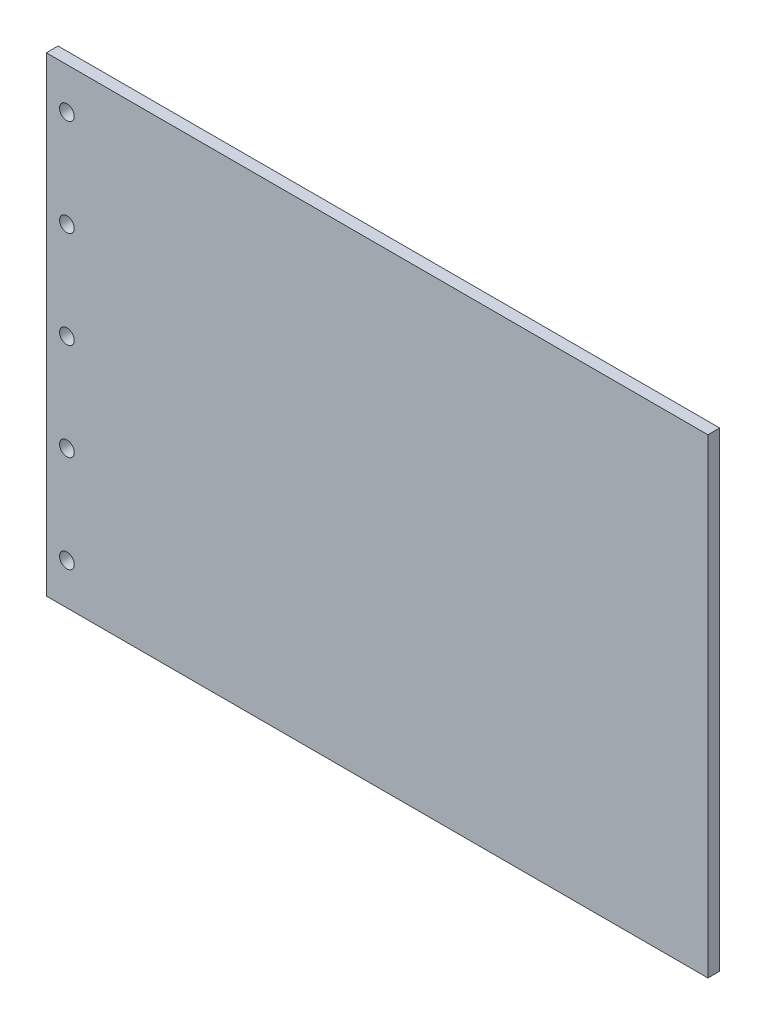
SolidWorks part; units mm, degrees
material "Сталь 3 ГОСТ 535-88"
ref_plane "Спереди" through (0, 0, 0) normal (0, 0, 1) x (1, 0, 0)
ref_plane "Сверху" through (0, 0, 0) normal (0, 1, 0) x (1, 0, 0)
ref_plane "Справа" through (0, 0, 0) normal (1, 0, 0) x (0, 0, -1)
sketch "Эскиз1" plane through (0, 0, 0) normal (0, 0, 1) x (1, 0, 0)
  line L0 (7, 80) -> (0, 80) construction
  line L1 (0, 0) -> (225, 0)
  line L2 (0, 0) -> (0, 160)
  line L3 (0, 160) -> (225, 160)
  line L4 (225, 0) -> (225, 160)
  line L5 (7, 80) -> (7, 0) construction
  line L6 (7, 80) -> (7, 160) construction
  circle A0 centre (7, 80) radius 2.5
  circle A1 centre (7, 47) radius 2.5
  circle A2 centre (7, 14) radius 2.5
  circle A3 centre (7, 113) radius 2.5
  circle A4 centre (7, 146) radius 2.5
  dimension "D3" = 5
  dimension "D4" = 7
  dimension "D5" = 33
  dimension "D6" = 33
  dimension "D7" = 33
  dimension "D8" = 33
  dimension "D1" = 225
  dimension "D2" = 160
extrude "Бобышка-Вытянуть1" add sketch "Эскиз1" along normal blind 4
